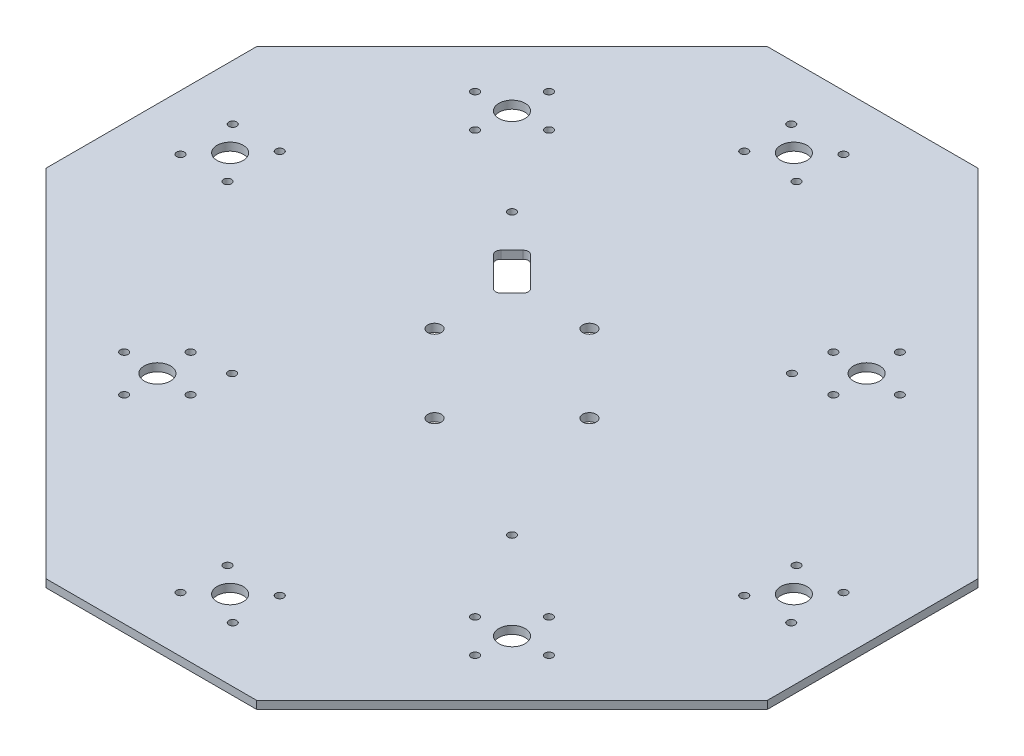
SolidWorks part; units mm, degrees
ref_plane "Front Plane" through (0, 0, 0) normal (0, 0, 1) x (1, 0, 0)
ref_plane "Top Plane" through (0, 0, 0) normal (0, 1, 0) x (1, 0, 0)
ref_plane "Right Plane" through (0, 0, 0) normal (1, 0, 0) x (0, 0, -1)
sketch "Sketch1" plane through (0, 0, 0) normal (0, 1, 0) x (1, 0, 0)
  line L0 (0, 0) -> (-88.7419, -88.7419) construction
  line L1 (68.75, -165.9772) -> (165.9772, -68.75) construction
  line L2 (165.9772, -68.75) -> (165.9772, 68.75) construction
  line L3 (165.9772, 68.75) -> (68.75, 165.9772) construction
  line L4 (68.75, 165.9772) -> (-68.75, 165.9772) construction
  line L5 (-68.75, 165.9772) -> (-165.9772, 68.75) construction
  line L6 (-165.9772, 68.75) -> (-165.9772, -68.75) construction
  line L7 (-165.9772, -68.75) -> (-68.75, -165.9772) construction
  line L8 (-68.75, -165.9772) -> (68.75, -165.9772) construction
  line L9 (117.3636, 117.3636) -> (-117.3636, -117.3636) construction
  line L10 (0, 0) -> (88.7419, 88.7419) construction
  line L11 (-88.7419, -88.7419) -> (-11.5066, -165.9772) construction
  line L12 (-11.5066, -165.9772) -> (-165.9772, -11.5066) construction
  line L13 (88.7419, 88.7419) -> (165.9772, 11.5066) construction
  line L14 (165.9772, 11.5066) -> (11.5066, 165.9772) construction
  circle A0 centre (0, 0) radius 165.9772 construction
  dimension "D1" = 137.5
sketch "Sketch3" plane through (0, 0, 0) normal (0, 1, 0) x (1, 0, 0)
  line L3 (146.9176, 30.5662) -> (11.5066, 165.9772)
  line L4 (11.5066, 165.9772) -> (-68.75, 165.9772)
  line L5 (-68.75, 165.9772) -> (-165.9772, 68.75)
  line L6 (-165.9772, 68.75) -> (-165.9772, -11.5066)
  line L7 (-165.9772, -11.5066) -> (-30.5662, -146.9176)
  line L8 (-68.75, 165.9772) -> (146.9176, -49.6904) construction
  line L9 (-165.9772, 68.75) -> (49.6904, -146.9176) construction
  line L10 (49.6904, -146.9176) -> (146.9176, -49.6904)
  line L11 (146.9176, 30.5662) -> (146.9176, -49.6904)
  line L12 (49.6904, -146.9176) -> (-30.5662, -146.9176)
extrude "Boss-Extrude2" add sketch "Sketch3" along normal blind 3
hole_wizard "13/64 (0.20313) Diameter Hole1" positions "Sketch8" profile "Sketch7" hole size "13/64" standard "ANSI Inch" end condition up to next
sketch "Sketch8" plane through (0, 0, 0) normal (0, -1, 0) x (-1, 0, 0)
  point P0 (39.0298, 9.5282)
  point P3 (9.5282, -19.9702)
  point P6 (-19.9702, 9.5314)
  point P9 (9.5314, 39.0298)
sketch "Sketch7" plane through (-39.0298, 0, -9.5282) normal (1, 0, 0) x (0, 0, -1)
  line L0 (0, 0) -> (0, 3)
  line L1 (0, 3) -> (2.5798, 3)
  line L2 (2.5798, 3) -> (2.5798, 0)
  line L5 (2.5798, 0) -> (0, 0)
  line L11 (0, -6.35) -> (0, 107.95) construction
  dimension "Thru Hole Dia." = 5.1595
  dimension "Thru Hole Depth" = 3
sketch "Sketch11" plane through (0, 0, 0) normal (0, -1, 0) x (-1, 0, 0)
  line L0 (98.2717, -79.2121) -> (-79.2121, 98.2717)
  line L1 (165.9772, -11.5066) -> (30.5662, -146.9176) construction
  line L2 (-146.9176, 30.5662) -> (-11.5066, 165.9772) construction
  line L3 (-79.2121, 98.2717) -> (9.5298, 9.5298)
  line L4 (9.5298, 9.5298) -> (36.0463, 36.0463)
sketch "Sketch12" plane through (0, 0, 0) normal (0, -1, 0) x (1, 0, 0)
  line L0 (-9.5298, -9.5298) -> (-36.0463, -36.0463) construction
  line L1 (-36.0463, -36.0463) -> (-39.5818, -32.5108)
  line L2 (-36.0463, -36.0463) -> (-32.5108, -39.5818)
  line L3 (-32.5108, -39.5818) -> (-46.6529, -53.724)
  line L4 (-46.6529, -53.724) -> (-53.724, -46.6529)
  line L5 (-53.724, -46.6529) -> (-39.5818, -32.5108)
extrude "Cut-Extrude1" cut sketch "Sketch12" against normal through all
fillet "Fillet2" radius 2 1 edges at (-39.5818, 1.5, -32.5108) type face fillet first side face at (-46.6529, 1.5, -39.5818) second side face at (-36.0463, 1.5, -36.0463)
fillet "Fillet3" radius 2 1 edges at (-32.5108, 1.5, -39.5818) type face fillet first side face at (-35.3392, 1.5, -36.7534) second side face at (-39.5818, 1.5, -46.6529)
fillet "Fillet4" radius 2 1 edges at (-53.724, 1.5, -46.6529) type face fillet first side face at (-47.36, 1.5, -40.289) second side face at (-50.1884, 1.5, -50.1884)
fillet "Fillet5" radius 2 1 edges at (-46.6529, 1.5, -53.724) type face fillet first side face at (-40.289, 1.5, -47.36) second side face at (-49.4813, 1.5, -50.8956)
hole_wizard "Ø3.0mm Dowel Hole1" positions "Sketch15" profile "Sketch16" hole size "Ø3.0" standard "ANSI Metric" end condition up to next
sketch "Sketch15" plane through (0, 0, 0) normal (0, -1, 0) x (-1, 0, 0)
  point P0 (-76.3832, -90.4563)
  point P3 (-90.4539, -76.3841)
  point P6 (-77.796, -63.7276)
  point P9 (-63.7253, -77.7997)
  point P12 (-19.5121, -125.8676)
  point P15 (-19.5121, -107.9676)
  point P18 (0.3879, -125.8676)
  point P21 (0.3879, -107.9676)
  point P24 (63.6953, -58.7041)
  point P27 (76.3518, -71.362)
  point P30 (90.424, -57.2914)
  point P33 (77.7675, -44.6335)
  point P36 (144.9272, 38.5717)
  point P39 (127.0272, 38.5717)
  point P42 (127.0272, 18.6717)
  point P45 (144.9272, 18.6717)
  point P48 (96.8556, 82.7872)
  point P51 (82.785, 96.8594)
  point P54 (95.4429, 109.5159)
  point P57 (109.5135, 95.4437)
  point P60 (18.6717, 144.9272)
  point P63 (18.6717, 127.0272)
  point P66 (38.5717, 127.0272)
  point P69 (38.5717, 144.9272)
  point P72 (-58.7079, 63.6931)
  point P75 (-71.3644, 76.351)
  point P78 (-44.6357, 77.7637)
  point P81 (-57.2922, 90.4216)
  point P84 (-125.8676, -19.5121)
  point P87 (-107.9676, -19.5121)
  point P90 (-107.9676, 0.3879)
  point P93 (-125.8676, 0.3879)
  point P97 (0, 0)
  point P98 (0, 0)
  point P99 (0, 0)
  point P100 (0, 0)
  point P101 (0, 0)
  point P102 (0, 0)
  point P103 (0, 0)
  point P104 (0, 0)
  point P105 (0, 0)
  point P106 (0, 0)
  point P107 (0, 0)
  point P108 (0, 0)
  point P109 (0, 0)
  point P110 (0, 0)
  point P111 (0, 0)
  point P112 (0, 0)
  point P113 (0, 0)
  point P114 (0, 0)
  point P115 (0, 0)
  point P116 (0, 0)
  point P117 (0, 0)
  point P118 (0, 0)
  point P119 (0, 0)
  point P120 (0, 0)
  point P121 (0, 0)
  point P122 (0, 0)
  point P123 (0, 0)
  point P124 (0, 0)
  point P125 (0, 0)
  point P126 (0, 0)
  point P127 (0, 0)
  point P128 (0, 0)
sketch "Sketch16" plane through (76.3832, 0, 90.4563) normal (1, 0, 0) x (0, 0, -1)
  line L0 (0, 0) -> (0, 3)
  line L1 (0, 3) -> (1.5, 3)
  line L2 (1.5, 3) -> (1.5, 0)
  line L5 (1.5, 0) -> (0, 0)
  line L11 (0, -6.35) -> (0, 107.95) construction
  dimension "Thru Hole Dia." = 3
  dimension "Thru Hole Depth" = 3
hole_wizard "Ø10.0mm Dowel Hole1" positions "Sketch18" profile "Sketch17" hole size "Ø10.0" standard "ANSI Metric" end condition up to next
sketch "Sketch18" plane through (0, 3, 0) normal (0, 1, 0) x (1, 0, 0)
  point P0 (-135.9772, 28.6217)
  point P3 (-96.1492, 96.1515)
  point P6 (-28.6217, 135.9772)
  point P9 (58, 77.0574)
  point P12 (116.9176, -9.5621)
  point P15 (0, 0)
  point P16 (0, 0)
  point P17 (0, 0)
  point P18 (0, 0)
  point P19 (0, 0)
sketch "Sketch17" plane through (-135.9772, 3, -28.6217) normal (1, 0, 0) x (0, 0, 1)
  line L0 (0, 0) -> (0, 3)
  line L1 (0, 3) -> (5, 3)
  line L2 (5, 3) -> (5, 0)
  line L5 (5, 0) -> (0, 0)
  line L11 (0, -6.35) -> (0, 107.95) construction
  dimension "Thru Hole Dia." = 10
  dimension "Thru Hole Depth" = 3
hole_wizard "Ø10.0mm Dowel Hole2" positions "Sketch19" profile "Sketch20" hole size "Ø10.0" standard "ANSI Metric" end condition up to next
sketch "Sketch19" plane through (0, 3, 0) normal (0, 1, 0) x (1, 0, 0)
  point P0 (9.5621, -116.9176)
  point P3 (77.0896, -77.0919)
  point P6 (-77.0597, -57.9977)
  point P9 (0, 0)
  point P10 (0, 0)
  point P11 (0, 0)
sketch "Sketch20" plane through (9.5621, 3, 116.9176) normal (1, 0, 0) x (0, 0, 1)
  line L0 (0, 0) -> (0, 3)
  line L1 (0, 3) -> (5, 3)
  line L2 (5, 3) -> (5, 0)
  line L5 (5, 0) -> (0, 0)
  line L11 (0, -6.35) -> (0, 107.95) construction
  dimension "Thru Hole Dia." = 10
  dimension "Thru Hole Depth" = 3
hole_wizard "Ø3.0mm Dowel Hole2" positions "Sketch21" profile "Sketch22" hole size "Ø3.0" standard "ANSI Metric" end condition up to next
sketch "Sketch21" plane through (0, 0, 0) normal (0, -1, 0) x (-1, 0, 0)
  point P0 (62.8254, -43.771)
  point P3 (-43.771, -43.7658)
  point P6 (62.8306, 62.8254)
  point P9 (-43.7658, 62.8306)
  point P13 (0, 0)
  point P14 (0, 0)
  point P15 (0, 0)
  point P16 (0, 0)
sketch "Sketch22" plane through (-62.8254, 0, 43.771) normal (1, 0, 0) x (0, 0, -1)
  line L0 (0, 0) -> (0, 3)
  line L1 (0, 3) -> (1.5, 3)
  line L2 (1.5, 3) -> (1.5, 0)
  line L5 (1.5, 0) -> (0, 0)
  line L11 (0, -6.35) -> (0, 107.95) construction
  dimension "Thru Hole Dia." = 3
  dimension "Thru Hole Depth" = 3
